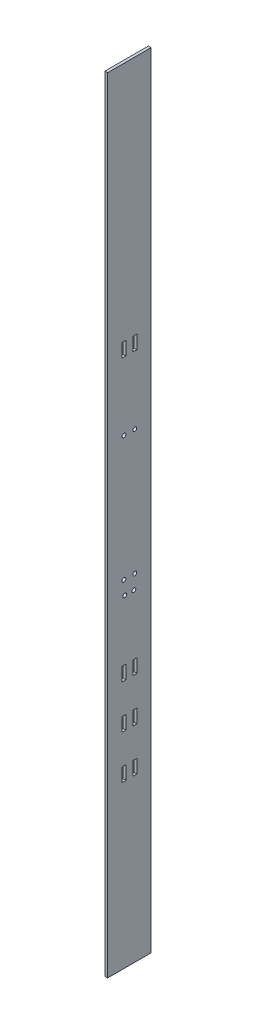
SolidWorks part; units mm, degrees
ref_plane "Front Plane" through (0, 0, 0) normal (0, 0, 1) x (1, 0, 0)
ref_plane "Top Plane" through (0, 0, 0) normal (0, 1, 0) x (1, 0, 0)
ref_plane "Right Plane" through (0, 0, 0) normal (1, 0, 0) x (0, 0, -1)
sketch "Sketch1" plane through (0, 0, 0) normal (1, 0, 0) x (0, 0, -1)
  line L1 (-25.4, 457.2) -> (25.4, 457.2)
  line L2 (-25.4, 457.2) -> (-25.4, -457.2)
  line L3 (-25.4, -457.2) -> (25.4, -457.2)
  line L4 (25.4, 457.2) -> (25.4, -457.2)
  line L5 (-25.4, 457.2) -> (25.4, -457.2) construction
  line L6 (-25.4, -457.2) -> (25.4, 457.2) construction
  point P0 (0, 0)
  dimension "D1" = 914.4
  dimension "D2" = 50.8
extrude "Boss-Extrude1" add sketch "Sketch1" along normal blind 3.175
sketch "Sketch2" plane through (3.175, 0, 0) normal (1, 0, 0) x (0, 0, -1)
  line L0 (-25.4, -457.2) -> (25.4, -457.2) construction
  line L1 (4, -201.6125) -> (8.7625, -201.6125)
  line L2 (4, -201.6125) -> (4, -217.4875)
  line L3 (4, -217.4875) -> (8.7625, -217.4875)
  line L4 (8.7625, -201.6125) -> (8.7625, -217.4875)
  line L5 (4, -201.6125) -> (8.7625, -217.4875) construction
  line L6 (4, -217.4875) -> (8.7625, -201.6125) construction
  point P0 (6.3813, -209.55)
  dimension "D1" = 4.7625
  dimension "D2" = 15.875
  dimension "D3" = 239.7125
  dimension "D4" = 4
extrude "Cut-Extrude1" cut sketch "Sketch2" against normal through all
mirror "Mirror1" about plane through (0, 0, 0) normal (0, 0, 1) of "Cut-Extrude1"
pattern_linear "LPattern1" count 2 spacing 50.8 along (0, 1, 0) count 2 spacing 50.8 along (0, -1, 0) of "Mirror1"
sketch "Sketch3" plane through (3.175, 0, 0) normal (1, 0, 0) x (0, 0, -1)
  line L0 (8.7625, -150.8125) -> (4, -150.8125) construction
  line L1 (4, 176.2125) -> (8.7625, 176.2125)
  line L2 (4, 176.2125) -> (4, 160.3375)
  line L3 (4, 160.3375) -> (8.7625, 160.3375)
  line L4 (8.7625, 176.2125) -> (8.7625, 160.3375)
  line L5 (4, 176.2125) -> (8.7625, 160.3375) construction
  line L6 (4, 160.3375) -> (8.7625, 176.2125) construction
  line L7 (8.7625, -166.6875) -> (8.7625, -150.8125) construction
  line L8 (4, -150.8125) -> (4, -166.6875) construction
  line L9 (0, 0) -> (0, 53.0447) construction
  line L10 (-4, 160.3375) -> (-8.7625, 176.2125) construction
  line L11 (-4, 176.2125) -> (-8.7625, 160.3375) construction
  line L12 (-8.7625, 176.2125) -> (-8.7625, 160.3375)
  line L13 (-4, 160.3375) -> (-8.7625, 160.3375)
  line L14 (-4, 176.2125) -> (-4, 160.3375)
  line L15 (-4, 176.2125) -> (-8.7625, 176.2125)
  point P0 (6.3812, 168.275)
  point P12 (6.3812, 160.3375)
  point P19 (-6.3812, 168.275)
  dimension "D1" = 311.15
extrude "Cut-Extrude2" cut sketch "Sketch3" against normal through all
hole_wizard "#8 Clearance Hole1" positions "Sketch4" profile "Sketch5" hole size "#8" standard "ANSI Inch" end condition through all
sketch "Sketch4" plane through (3.175, 0, 0) normal (1, 0, 0) x (0, 0, -1)
  point P0 (6.35, -64.5237)
  point P3 (-6.35, -64.5237)
  point P6 (6.35, 81.272)
  point P9 (-6.35, 81.272)
  point P12 (5.25, -80.7656)
  point P15 (-5.25, -80.7656)
sketch "Sketch5" plane through (3.175, -64.5237, -6.35) normal (0, 1, 0) x (0, 0, -1)
  line L0 (0, 0) -> (0, 3.175)
  line L1 (0, 3.175) -> (2.2479, 3.175)
  line L2 (2.2479, 3.175) -> (2.2479, 0)
  line L5 (2.2479, 0) -> (0, 0)
  line L11 (0, -6.35) -> (0, 107.95) construction
  dimension "Thru Hole Dia." = 4.4958
  dimension "Thru Hole Depth" = 3.175
